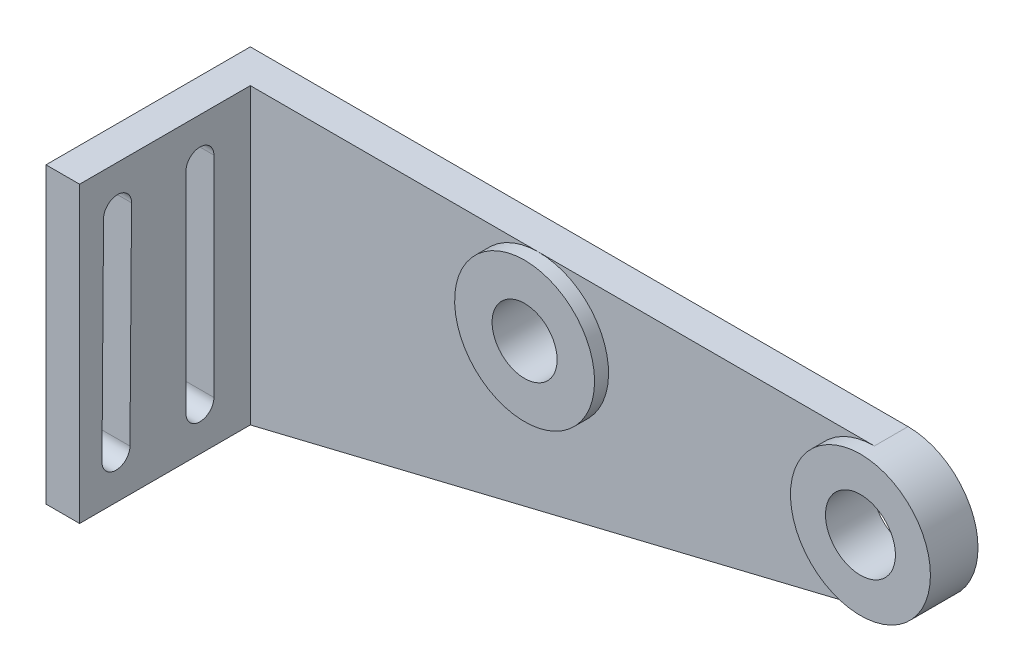
SolidWorks part; units mm, degrees
ref_plane "Front Plane" through (0, 0, 0) normal (0, 0, 1) x (1, 0, 0)
ref_plane "Top Plane" through (0, 0, 0) normal (0, 1, 0) x (1, 0, 0)
ref_plane "Right Plane" through (0, 0, 0) normal (1, 0, 0) x (0, 0, -1)
sketch "Sketch1" plane through (0, 0, 0) normal (0, 0, 1) x (1, 0, 0)
  line L0 (12, 0) -> (235, 0)
  line L1 (0, 0) -> (12, 0)
  line L2 (0, 0) -> (0, -105)
  line L3 (0, -105) -> (12, -105)
  line L4 (12, 0) -> (12, -105)
  line L6 (12, -105) -> (240.9116, -49.291)
  circle A1 centre (115, -25) radius 25
  circle A2 centre (115, -25) radius 11.6191
  circle A3 centre (235, -25) radius 25
  circle A4 centre (235, -25) radius 12.5
  dimension "D7" = 25
  dimension "D5" = 50
  dimension "D8" = 50
  dimension "D9" = 23.2382
  dimension "D1" = 235
  dimension "D2" = 105
  dimension "D3" = 25
  dimension "D4" = 12
  dimension "D6" = 115
extrude "Boss-Extrude41" add sketch "Sketch1" along normal blind 12 contours A3 L0 A1 L4 L6 | A1 A2 | A3 A4 region at (132.1777, -7.8223, 0) region at (63.5, -2.5184, 0) region at (252.1777, -7.8223, 0)
extrude "Boss-Extrude42" add sketch "Sketch1<11>" along normal blind 73 contours L4 L1 L2 L3 region at (6, -52.5, 0)
sketch "Sketch1<11>" plane through (0, 0, 0) normal (0, 0, 1) x (1, 0, 0) same geometry as "Sketch1"
extrude "Boss-Extrude43" add sketch "Sketch1<12>" along normal blind 5 from surface contours A1 A2 | A3 A4 region at (132.1777, -7.8223, 0) region at (252.1777, -7.8223, 0) starting at face at (130.4445, -37.9171, 12)
sketch "Sketch1<12>" plane through (0, 0, 0) normal (0, 0, 1) x (1, 0, 0) same geometry as "Sketch1"
sketch "Sketch2" plane through (12, 0, 0) normal (1, 0, 0) x (0, 0, -1)
  line L0 (-59.4349, -15) -> (-60, -90) construction
  line L1 (-54.435, -15.0377) -> (-55.0001, -90.0377)
  line L2 (-64.4348, -14.9623) -> (-64.9999, -89.9623)
  line L3 (-30, -15) -> (-30, -90) construction
  line L4 (-25, -15) -> (-25, -90)
  line L5 (-35, -15) -> (-35, -90)
  line L6 (0, -105) -> (0, -49.291) construction
  line L7 (-73, 0) -> (-12, 0) construction
  arc A0 (-54.435, -15.0377) -> (-64.4348, -14.9623) centre (-59.4349, -15) ccw
  arc A1 (-64.9999, -89.9623) -> (-55.0001, -90.0377) centre (-60, -90) ccw
  arc A2 (-25, -15) -> (-35, -15) centre (-30, -15) ccw
  arc A3 (-35, -90) -> (-25, -90) centre (-30, -90) ccw
  point P2 (-59.7174, -52.5)
  point P9 (-30, -52.5)
  dimension "D1" = 30
  dimension "D2" = 30
  dimension "D3" = 15
  dimension "D4" = 15
  dimension "D5" = 75
  dimension "D6" = 75
extrude "Cut-Extrude1" cut sketch "Sketch2" against normal through all
